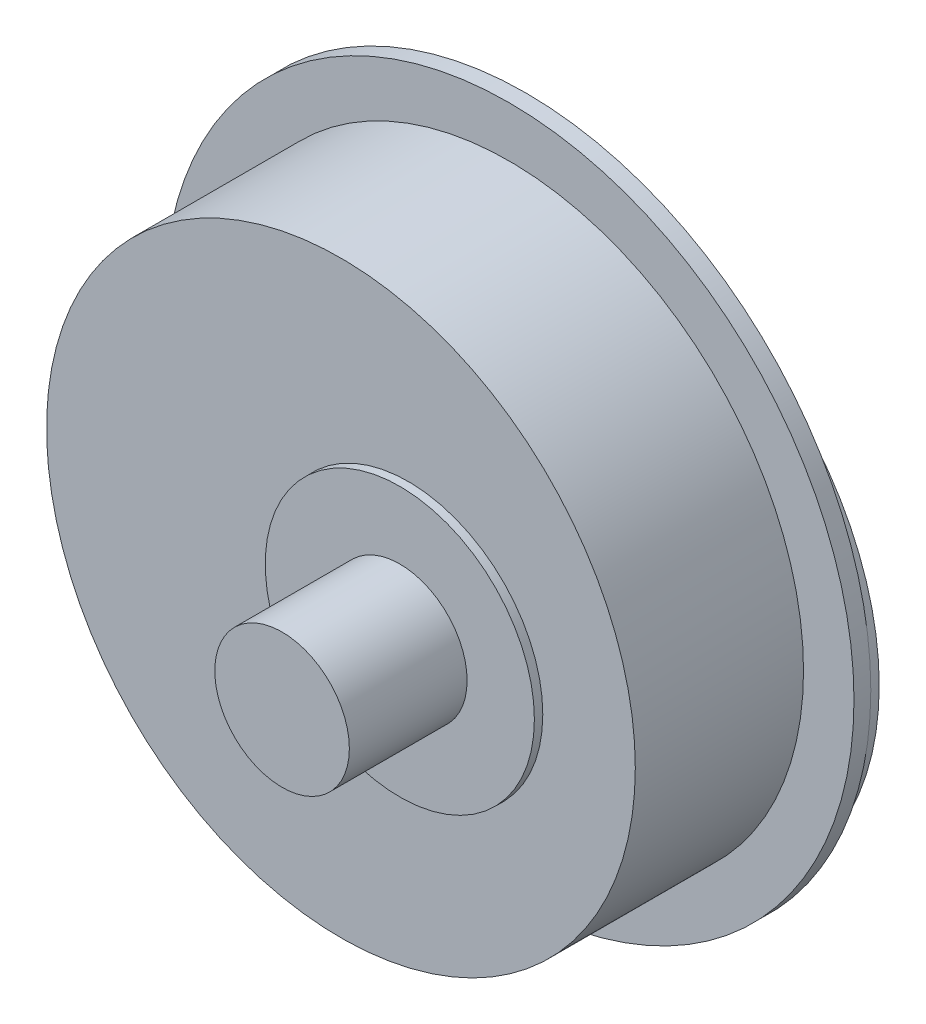
SolidWorks part; units mm, degrees
ref_plane "Front Plane" through (0, 0, 0) normal (0, 0, 1) x (1, 0, 0)
ref_plane "Top Plane" through (0, 0, 0) normal (0, 1, 0) x (1, 0, 0)
ref_plane "Right Plane" through (0, 0, 0) normal (1, 0, 0) x (0, 0, -1)
sketch "Sketch1" plane through (0, 0, 0) normal (0, 0, 1) x (1, 0, 0)
  line L0 (-5, 6.245) -> (-5, -6.245)
  circle A0 centre (0, 0) radius 8
  circle A1 centre (-4, 0) radius 17.5
  dimension "D1" = 35
  dimension "D2" = 16
  dimension "D4" = 5
  dimension "D3" = 4
extrude "Boss-Extrude1" add sketch "Sketch1" along normal blind 5 contours L0 A0 | A1 region at (0.928, 0, 0)
sketch "Sketch6" plane through (0, 0, 5) normal (0, 0, 1) x (1, 0, 0)
  circle A0 centre (-4, 0) radius 17.5
  circle A1 centre (-4, 0) radius 17.5 construction
extrude "Boss-Extrude7" add sketch "Sketch6" along normal blind 5
sketch "Sketch3" plane through (0, 0, 0) normal (0, 0, -1) x (-1, 0, 0)
  circle A0 centre (4, 0) radius 20.5
  circle A2 centre (4, 0) radius 17.5 construction
  circle M8 centre (4, 0) radius 17.5
  line M9 (5, 6.245) -> (5, -6.245)
  arc M10 (5, -6.245) -> (5, 6.245) centre (0, 0) cw
  dimension "D1" = 41
extrude "Boss-Extrude3" add sketch "Sketch3" along normal blind 1 contours A0 | M8 M10 M9 region at (15.9202, 0, 0) region at (-5.0954, 0, 0)
sketch "Sketch4" plane through (0, 0, 10) normal (0, 0, 1) x (1, 0, 0)
  circle A0 centre (0, 0) radius 8
  dimension "D1" = 16
extrude "Boss-Extrude5" add sketch "Sketch4" along normal blind 0.5
sketch "Sketch5" plane through (0, 0, 10.5) normal (0, 0, 1) x (1, 0, 0)
  circle A0 centre (0, 0) radius 4
  dimension "D1" = 8
extrude "Boss-Extrude6" add sketch "Sketch5" along normal blind 7
sketch "Sketch7" plane through (0, 0, -1) normal (0, 0, -1) x (-1, 0, 0)
  circle A0 centre (0, 0) radius 16.5
  circle A1 centre (4, 0) radius 20.5 construction
  arc M3 (5, -6.245) -> (5, 6.245) centre (0, 0) cw
  line M4 (5, 6.245) -> (5, -6.245)
extrude "Boss-Extrude8" add sketch "Sketch7" along normal blind 0.5 contours A0 M4 M3 region at (16.0333, 0, -1)
